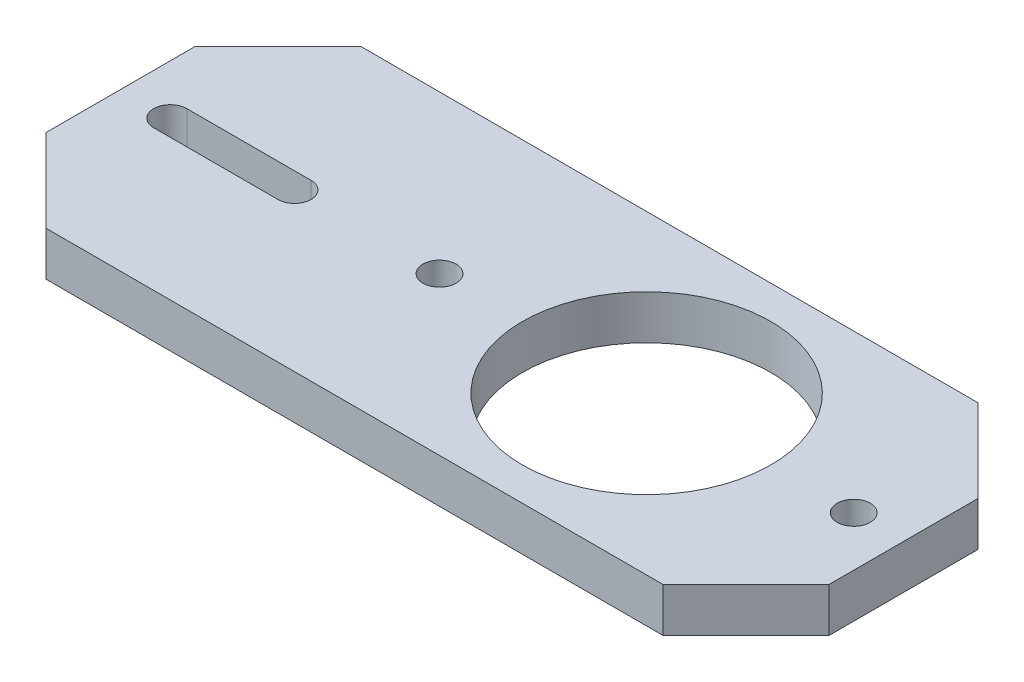
SolidWorks part; units mm, degrees
material "Pine"
ref_plane "Front Plane" through (0, 0, 0) normal (0, 0, 1) x (1, 0, 0)
ref_plane "Top Plane" through (0, 0, 0) normal (0, 1, 0) x (1, 0, 0)
ref_plane "Right Plane" through (0, 0, 0) normal (1, 0, 0) x (0, 0, -1)
sketch "Sketch1" plane through (0, 0, 0) normal (0, 1, 0) x (1, 0, 0)
  line L0 (-57.5, 2) -> (-42.5, 2)
  line L1 (-57.5, -2) -> (-42.5, -2)
  line L2 (-84.5376, 0) -> (67.9764, 0) construction
  line L3 (-50, 2) -> (-50, -2) construction
  line L4 (-63.5, 9) -> (-53.5, 19)
  line L5 (-53.5, 19) -> (21, 19)
  line L6 (-63.5, 9) -> (-63.5, -9)
  line L7 (-53.5, -19) -> (21, -19)
  line L8 (31, 9) -> (31, -9)
  line L9 (-63.5, -9) -> (-53.5, -19)
  line L10 (21, -19) -> (31, -9)
  line L11 (21, 19) -> (31, 9)
  circle A0 centre (-25, 0) radius 2
  circle A1 centre (25, 0) radius 2
  arc A2 (-42.5, -2) -> (-42.5, 2) centre (-42.5, 0) ccw
  arc A4 (-57.5, 2) -> (-57.5, -2) centre (-57.5, 0) ccw
  circle A5 centre (0, 0) radius 15
  point P19 (-63.5, 19)
  point P20 (31, -19)
  point P21 (-63.5, -19)
  point P22 (31, 19)
  dimension "D1" = 4
  dimension "D2" = 4
  dimension "D4" = 4
  dimension "D5" = 75
  dimension "D8" = 4
  dimension "D10" = 30
  dimension "D12" = 6
  dimension "D3" = 50
  dimension "D6" = 15
  dimension "D7" = 6
  dimension "D11" = 25
  dimension "D14" = 19
  dimension "D15" = 19
extrude "Boss-Extrude1" add sketch "Sketch1" against normal blind 5.333
equation "\"rod_diameter\"= 8"
equation "\"rod_hole_thickness\"= 4"
equation "\"rod_radius\"= \"rod_diameter\" / 2"
equation "\"platter_diameter\"= 320"
equation "\"platter_radius\"= \"platter_diameter\" / 2"
equation "\"extruder_mount_hole_spacing\"= 75"
equation "\"arm_rod_spacing\"= 40"
equation "\"motor_level_rod_spacing\"= 15"
equation "\"linear_bearing_diameter\"= 15"
equation "\"z_rod_spacing\"= 75"
equation "\"platter_rod_spacing\"= 50"
equation "\"rod_nut_thickness\"= 6.5"
equation "\"rod_nut_inscribed_diameter\"= 13"
equation "\"z_height\"= 400"
equation "\"gear_pitch\"=2"
equation "\"r_gear_teeth\"= 450"
equation "\"theta_gear_teeth\"= 385"
equation "\"D12@Sketch1\"=2 + \"rod_hole_thickness\""
equation "\"D14@Sketch1\"=15 +\"rod_hole_thickness\""
equation "\"D15@Sketch1\" = 15 + \"rod_hole_thickness\""
equation "\"D7@Sketch1\"=\"rod_hole_thickness\"+2"
equation "\"D5@Sketch1\"=\"extruder_mount_hole_spacing\""
equation "\"top_frame_spacing\"= 90"
equation "\"z_drive_rod_offset\"= 12"
equation "\"sheet_thickness\"=5.333"
equation "\"sheet_tab_hole_thickness\"= \"sheet_thickness\""
equation "\"sheet_tab_width\"= \"sheet_thickness\"*2"
equation "\"sheet_double_tab_width\"= 35"
equation "\"sheet_bolt_diameter\"= 3"
equation "\"sheet_bolt_length\"= 16"
equation "\"sheet_nut_diameter\"= 5.5"
equation "\"sheet_nut_thickness\"= 2.5"
equation "\"sheet_nut_depth\"= 10"
equation "\"bearing_outside_diameter\"= 22"
equation "\"bearing_thickness\"= 7"
equation "\"corner_part_thickness\"= \"sheet_thickness\" + \"bearing_thickness\""
equation "\"setscrew_nut_diameter\"= 6"
equation "\"setscrew_nut_thickness\"= 3"
equation "\"setscrew_bolt_diameter\"= 3"
equation "\"motor_shaft_diameter\"= 5.7"
equation "\"D1@Boss-Extrude1\"= \"sheet_thickness\""
